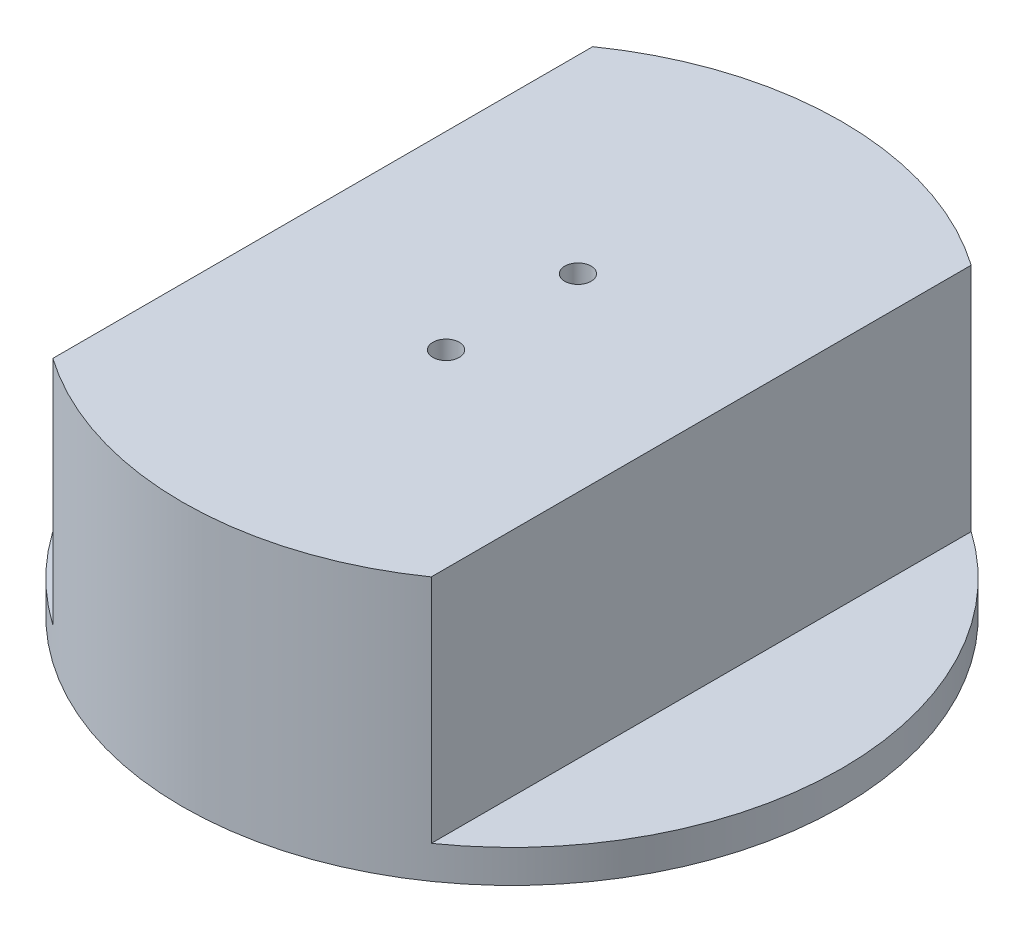
SolidWorks part; units mm, degrees
ref_plane "Ön Düzlem" through (0, 0, 0) normal (0, 0, 1) x (1, 0, 0)
ref_plane "Üst Düzlem" through (0, 0, 0) normal (0, 1, 0) x (1, 0, 0)
ref_plane "Sağ Düzlem" through (0, 0, 0) normal (1, 0, 0) x (0, 0, -1)
sketch "ara düzlem" plane through (0, 0, 0) normal (0, 1, 0) x (1, 0, 0)
  line L0 (-28.7, 40.9428) -> (-28.7, -40.9428)
  line L1 (0, 0) -> (0, 50) construction
  line L2 (28.7, 40.9428) -> (28.7, -40.9428)
  circle A0 centre (0, 0) radius 50
  point P5 (14.6186, 0)
  point P8 (-50, 0)
  dimension "D1" = 100
  dimension "D2" = 21.3
extrude "base" add sketch "ara düzlem" along normal blind 5 contours L0 A0 | L2 A0 L0 | L2 A0 region at (0, 0, 0) region at (-37.3976, 0, 0) region at (37.3976, 0, 0)
extrude "Yükseklik-Ekstrüzyon2" add sketch "Çizim1<3>" along normal blind 40 contours L2 A0 L0 region at (0, 0, 0)
sketch "Çizim1<3>" plane through (0, 0, 0) normal (0, 1, 0) x (1, 0, 0) same geometry as "ara düzlem"
sketch "Çizim2" plane through (0, 40, 0) normal (0, 1, 0) x (1, 0, 0)
  line L0 (0, 0) -> (28.7, 0) construction
  line L1 (28.7, 40.9428) -> (28.7, -40.9428) construction
  circle A0 centre (0, 10) radius 2
  circle A2 centre (0, -10) radius 2
  point P9 (0, 0)
  dimension "D1" = 4
  dimension "D2" = 10
extrude "banana slotları" cut sketch "Çizim2" against normal through all
